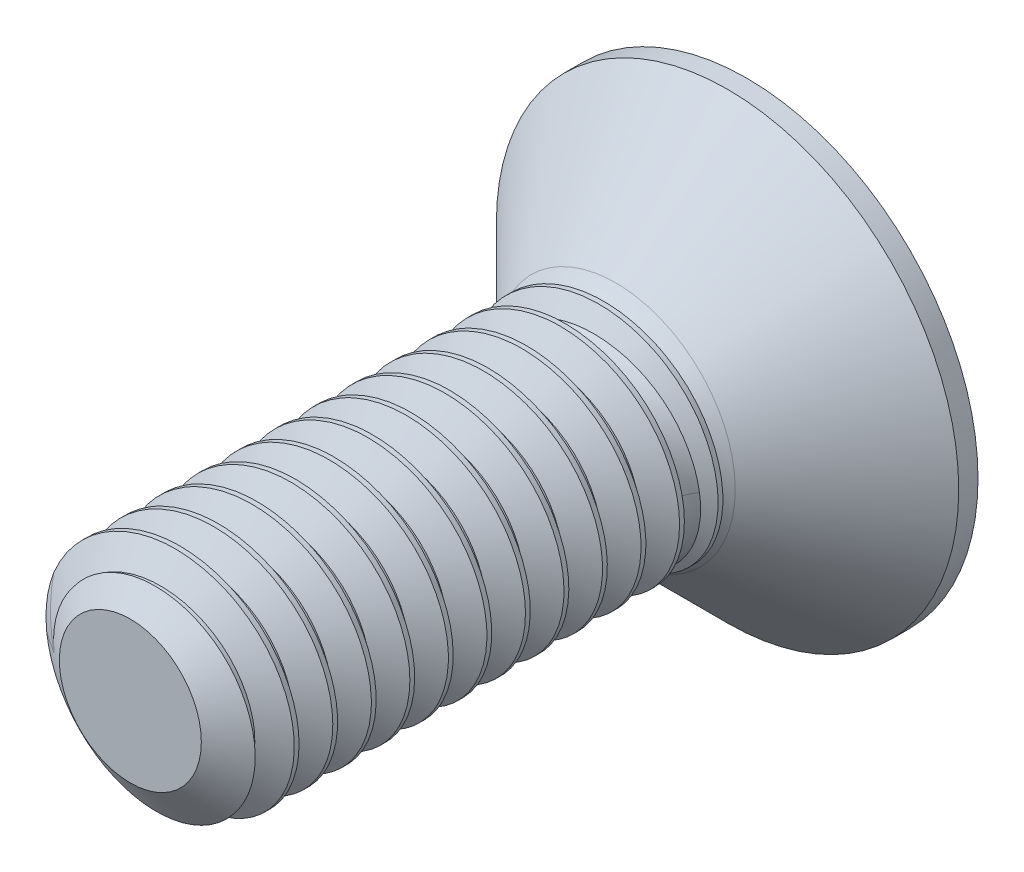
SolidWorks part; units mm, degrees
material "Alloy Steel"
ref_plane "Front Plane" through (0, 0, 0) normal (0, 0, 1) x (1, 0, 0)
ref_plane "Top Plane" through (0, 0, 0) normal (0, 1, 0) x (1, 0, 0)
ref_plane "Right Plane" through (0, 0, 0) normal (1, 0, 0) x (0, 0, -1)
sketch "Sketch1" plane through (0, 0, 0) normal (0, 0, 1) x (1, 0, 0)
  circle A0 centre (0, 0) radius 1.5
  dimension "OD" = 3
extrude "Extrude1" add sketch "Sketch1" against normal blind 8
sketch "Sketch2" plane through (0, 0, 0) normal (0, 0, 1) x (1, 0, 0)
  circle A0 centre (0, 0) radius 1.5 construction
  circle A1 centre (0, 0) radius 1.5
curve "Helix/Spiral1" pitch 0.5 height 8.5 radius 1.5 centre (0, 0, 0) axis (0, 0, -1) start towards (0, 1, 0) parameters "pitch"=0.5
sketch "Sketch3" plane through (0, 0, 0) normal (1, 0, 0) x (0, 0, -1)
  line L0 (-0.4375, 1.5) -> (-0.25, 1.1752)
  line L1 (-0.25, 1.1752) -> (-0.1875, 1.1752)
  line L2 (-0.1875, 1.1752) -> (0, 1.5)
  line L3 (-0.4375, 1.5) -> (0, 1.5)
  line L4 (-0.2188, 1.5) -> (-0.2188, 1.1752) construction
  line L5 (-0.3438, 1.3376) -> (-0.0937, 1.3376) construction
  line L6 (0, 1.5) -> (0, -1.5) construction
  dimension "D1" = 0.0625
  dimension "D2" = 0.25
  dimension "D3" = 60
sweep "Cut-Sweep1" cut profiles "Sketch3" path "Helix/Spiral1"
sketch "Sketch4" plane through (0, 0, 0) normal (1, 0, 0) x (0, 0, -1)
  line L0 (0.4053, 1.5) -> (0, 0.9212)
  line L1 (0, 0.9212) -> (0, 1.5)
  line L2 (0.4053, 1.5) -> (0, 1.5)
  line L3 (-0.4375, 1.5) -> (0, 1.5) construction
  line L4 (0, 0) -> (7.0209, 0) construction
  dimension "D1" = 55
  dimension "D2" = 0.254
revolve "Cut-Revolve1" cut sketch "Sketch4" angle 360 about L4
sketch "Sketch5" plane through (0, 0, 0) normal (1, 0, 0) x (0, 0, -1)
  line L0 (8, -1.1822) -> (8, 1.0703) construction
  line L1 (8, 1.55) -> (18.1906, 1.55)
  line L2 (8, 1.55) -> (8, 0)
  line L3 (8, 0) -> (18, 0)
  line L4 (18, 1.2198) -> (18, 0)
  line L5 (18.1906, 1.55) -> (18, 1.2198)
  line L6 (0, 0) -> (9.9695, 0) construction
  point P3 (18, 1.55)
  point P10 (18, 1.55)
  dimension "D1" = 0.3302
  dimension "Thread min" = 18
  dimension "D2" = 0.05
  dimension "D3" = 30
revolve "partially thread" [suppressed] add sketch "Sketch5" angle 360 about L6
sketch "Sketch6" plane through (0, 0, -8) normal (0, 0, -1) x (-1, 0, 0)
  circle A0 centre (0, 0) radius 3
  dimension "head dia" = 6
extrude "Extrude2" add sketch "Sketch6" against normal blind 1.7
sketch "Sketch10" plane through (0, 0, 0) normal (1, 0, 0) x (0, 0, -1)
  line L0 (7.75, -3) -> (6.3, -1.55)
  line L1 (6.3, -1.55) -> (6.3, -3)
  line L2 (7.75, -3) -> (6.3, -3)
  line L3 (0, 0) -> (6.3, 0) construction
  line L4 (6.3, 3) -> (6.3, -3) construction
  line L5 (7.75, 3) -> (6.3, 3) construction
  line L6 (6.3, 1.55) -> (6.3, 3) construction
  line L7 (7.75, 3) -> (6.3, 1.55) construction
  line L8 (6.3, 3) -> (6.3, -3) construction
  line L9 (6.3, 1.55) -> (6.3, -1.55) construction
  dimension "D1" = 45
  dimension "D2" = 0.05
revolve "Cut-Revolve2" cut sketch "Sketch10" angle 360 about L3
sketch "Sketch11" plane through (0, 0, 0) normal (1, 0, 0) x (0, 0, -1)
  line L0 (-0.25, 1.1752) -> (-0.1875, 1.1752) construction
  line L1 (7.75, 3) -> (6.3, 1.55) construction
  line L2 (5.3953, 1.1752) -> (5.3953, 0)
  line L3 (5.3953, 0) -> (6.3, 0)
  line L4 (6.3, 1.55) -> (6.3, 0)
  line L5 (0, 0) -> (6.3, 0) construction
  arc A0 (6.3, 1.55) -> (5.3953, 1.1752) centre (5.3953, 2.4547) cw
revolve "Revolve1" add sketch "Sketch11" angle 360 about L3
sketch "Sketch7" plane through (0, 0, -8) normal (0, 0, 1) x (1, 0, 0)
  line L1 (0, 1.1547) -> (-1, 0.5774)
  line L2 (-1, 0.5774) -> (-1, -0.5774)
  line L3 (-1, -0.5774) -> (0, -1.1547)
  line L4 (0, -1.1547) -> (1, -0.5774)
  line L5 (1, -0.5774) -> (1, 0.5774)
  line L6 (1, 0.5774) -> (0, 1.1547)
  circle A0 centre (0, 0) radius 1 construction
  dimension "hex dia" = 2
extrude "Cut-Extrude1" cut sketch "Sketch7" along normal blind 1.5
sketch "Sketch8" plane through (0, 0, -8) normal (0, 0, 1) x (1, 0, 0)
  circle A0 centre (0, 0) radius 1.1547
extrude "Cut-Extrude2" cut sketch "Sketch8" along normal through all draft 45
sketch "Sketch9" plane through (0, 0, 0) normal (1, 0, 0) x (0, 0, -1)
  line L0 (0, 1.5) -> (0, -1.5) construction
  line L1 (2.75, 1.5) -> (2.75, -1.5) construction
  line L2 (6.3, 1.5) -> (6.3, -1.5) construction
  line L3 (6.3, -1.55) -> (6.3, -3) construction
  dimension "D1" = 2.75
equation "\"D3@Helix/Spiral1\" = \"screw length@Extrude1\"+\"pitch@Helix/Spiral1\""
equation "\"D1@Sketch3\" = \"pitch@Helix/Spiral1\"*.125"
equation "\"D2@Sketch3\" = \"pitch@Helix/Spiral1\"*.5"
equation "\"D1@Cut-Extrude1\" = \"hex dia@Sketch7\"*.75"
equation "\"D1@Sketch9\" = \"pitch@Helix/Spiral1\"*5.5"
equation "\"D2@Sketch10\" = \"D2@Sketch5\""
